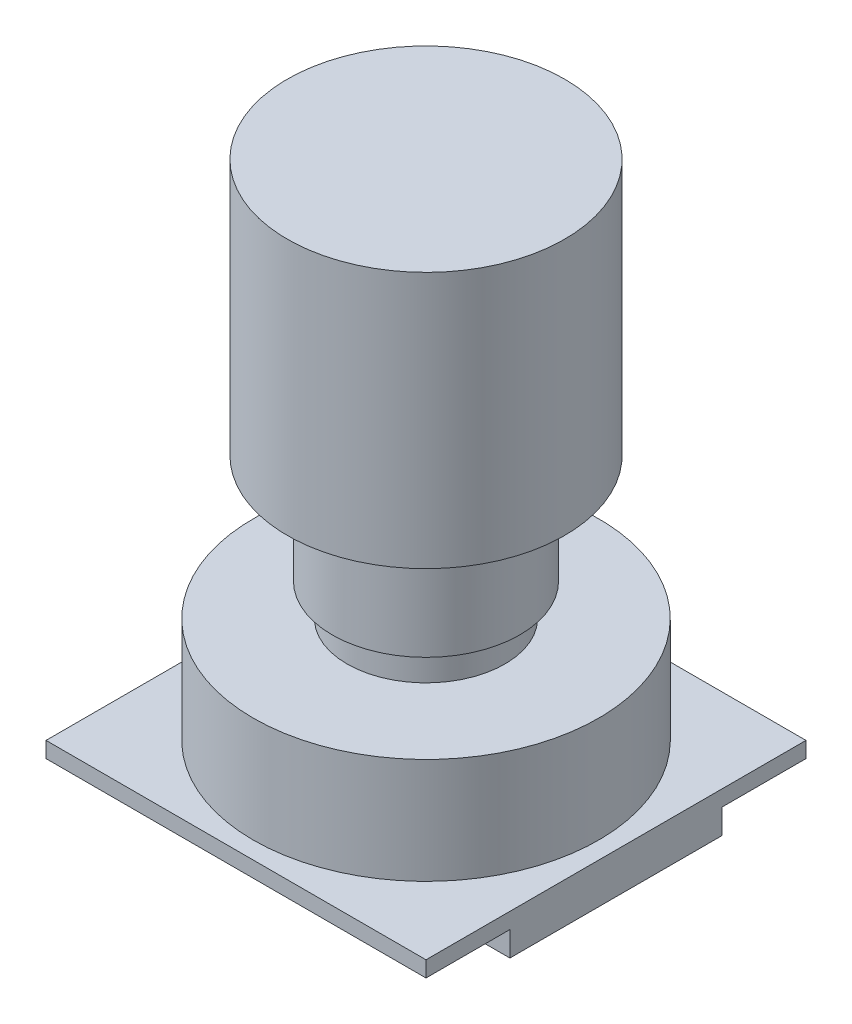
SolidWorks part; units mm, degrees
ref_plane "Front Plane" through (0, 0, 0) normal (0, 0, 1) x (1, 0, 0)
ref_plane "Top Plane" through (0, 0, 0) normal (0, 1, 0) x (1, 0, 0)
ref_plane "Right Plane" through (0, 0, 0) normal (1, 0, 0) x (0, 0, -1)
sketch "Sketch1" plane through (0, 0, 0) normal (0, 1, 0) x (1, 0, 0)
  line L1 (-19.25, -19.25) -> (19.25, -19.25)
  line L2 (-19.25, -19.25) -> (-19.25, 19.25)
  line L3 (-19.25, 19.25) -> (19.25, 19.25)
  line L4 (19.25, -19.25) -> (19.25, 19.25)
  line L5 (-19.25, -19.25) -> (19.25, 19.25) construction
  line L6 (-19.25, 19.25) -> (19.25, -19.25) construction
  point P0 (0, 0)
  dimension "D1" = 38.5
extrude "Boss-Extrude1" add sketch "Sketch1" along normal blind 1.6
sketch "Sketch2" plane through (0, 1.6, 0) normal (0, 1, 0) x (1, 0, 0)
  circle A0 centre (0, 0) radius 17.5
  dimension "D1" = 35
extrude "Boss-Extrude2" add sketch "Sketch2" along normal blind 10.7
sketch "Sketch3" plane through (0, 12.3, 0) normal (0, 1, 0) x (1, 0, 0)
  circle A0 centre (0, 0) radius 8
  dimension "D1" = 16
extrude "Boss-Extrude3" add sketch "Sketch3" along normal blind 3.3
sketch "Sketch4" plane through (0, 15.6, 0) normal (0, 1, 0) x (1, 0, 0)
  circle A0 centre (0, 0) radius 9.5
  dimension "D1" = 19
extrude "Boss-Extrude4" add sketch "Sketch4" along normal blind 11
sketch "Sketch5" plane through (0, 26.6, 0) normal (0, 1, 0) x (1, 0, 0)
  circle A0 centre (0, 0) radius 14.05
  dimension "D1" = 28.1
extrude "Boss-Extrude5" add sketch "Sketch5" along normal blind 26
sketch "Sketch7" plane through (0, 0, 0) normal (0, -1, 0) x (1, 0, 0)
  line L0 (19.25, 19.25) -> (19.25, -19.25) construction
  line L1 (19.25, -10.75) -> (13.25, -10.75)
  line L2 (19.25, -10.75) -> (19.25, 10.75)
  line L3 (19.25, 10.75) -> (13.25, 10.75)
  line L4 (13.25, -10.75) -> (13.25, 10.75)
  line L5 (19.25, -19.25) -> (-19.25, -19.25) construction
  line L6 (-19.25, 19.25) -> (19.25, 19.25) construction
  dimension "D1" = 8.5
  dimension "D2" = 8.5
  dimension "D3" = 6
extrude "Boss-Extrude6" add sketch "Sketch7" along normal blind 2.5
equation "\"D1@Boss-Extrude2\"=12.2-1.5"
equation "\"D1@Boss-Extrude6\"=4-1.5"
